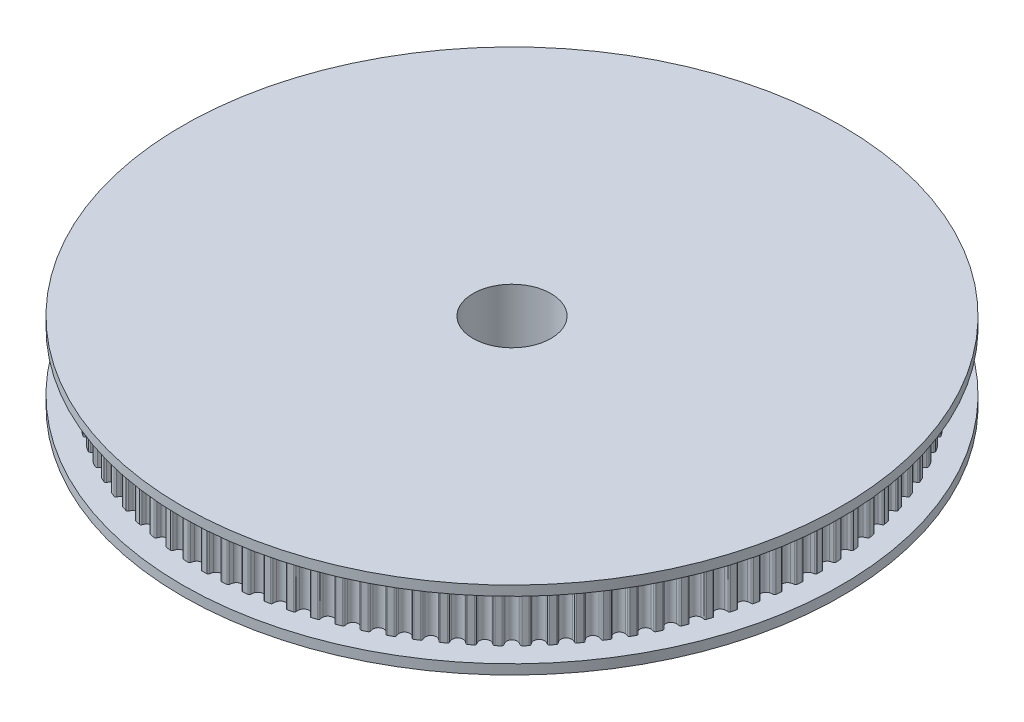
SolidWorks part; units mm, degrees
ref_plane "Front Plane" through (0, 0, 0) normal (0, 0, 1) x (1, 0, 0)
ref_plane "Top Plane" through (0, 0, 0) normal (0, 1, 0) x (1, 0, 0)
ref_plane "Right Plane" through (0, 0, 0) normal (1, 0, 0) x (0, 0, -1)
sketch "Sketch1" plane through (0, 0, 0) normal (0, 1, 0) x (1, 0, 0)
  circle A0 centre (0, 0) radius 31.831
  dimension "D1" = 63.662
extrude "Boss-Extrude1" add sketch "Sketch1" along normal mid plane 6
sketch "Sketch2" plane through (0, 0, 0) normal (0, 1, 0) x (1, 0, 0)
  line L0 (0, 0) -> (0, 31.577) construction
  line L1 (0, 0) -> (0.9857, 31.3665) construction
  line L2 (0, 31.577) -> (0, 31.831)
  line L3 (0.9857, 31.3665) -> (0.9998, 31.8153) construction
  line L4 (0.9998, 31.8153) -> (1.3996, 31.8002) construction
  line L5 (1.3996, 31.8002) -> (1.3902, 31.5521) construction
  line L6 (1.9827, 31.5147) -> (1.9987, 31.7682)
  arc A1 (0, 31.577) -> (0.2483, 31.576) centre (0, 0) cw
  arc A2 (0.2483, 31.576) -> (0.3962, 31.4425) centre (0.2471, 31.426) cw
  arc A3 (0.3962, 31.4425) -> (0.4813, 31.1351) centre (1.3902, 31.5521) ccw
  arc A4 (0.4813, 31.1351) -> (1.4746, 31.1038) centre (0.9857, 31.3665) ccw
  circle A5 centre (0, 0) radius 31.831 construction
  arc A6 (0, 31.831) -> (1.9987, 31.7682) centre (0, 0) cw
  arc A7 (1.5789, 31.4053) -> (1.4746, 31.1038) centre (0.5937, 31.5771) cw
  arc A8 (1.7349, 31.5293) -> (1.5789, 31.4053) centre (1.7266, 31.3795) ccw
  arc A9 (1.9827, 31.5147) -> (1.7349, 31.5293) centre (0, 0) ccw
  dimension "D2" = 0.15
  dimension "D3" = 1
  dimension "D4" = 0.555
  dimension "D1" = 1.8
  dimension "D5" = 0.254
  dimension "D6" = 0.4
  dimension "D7" = 1.004
extrude "Cut-Extrude1" cut sketch "Sketch2" against normal through all both and the other way through all
pattern_circular "CirPattern1" count 100 over 360 about axis through (0, 3, 0) along (0, -1, 0) of "Cut-Extrude1"
sketch "Sketch3" plane through (0, 0, 0) normal (0, 1, 0) x (1, 0, 0)
  circle A0 centre (0, 0) radius 33.831
  dimension "D1" = 67.662
extrude "Boss-Extrude2" add sketch "Sketch3" along normal blind 1 from surface starting at face at (0, 3, 0)
extrude "Boss-Extrude3" add sketch "Sketch3<2>" against normal blind 1 from surface starting at face at (0, -3, 0)
sketch "Sketch3<2>" plane through (0, 0, 0) normal (0, 1, 0) x (1, 0, 0) same geometry as "Sketch3"
sketch "Sketch4" plane through (0, 0, 0) normal (0, 1, 0) x (1, 0, 0)
  circle A0 centre (0, 0) radius 4
  dimension "D1" = 8
extrude "Cut-Extrude2" cut sketch "Sketch4" against normal through all both and the other way through all
equation "\"n\"= 100"
equation "\"p\"= 2mm"
equation "\"pd\"= ( \"n\" * \"p\" ) / pi"
equation "\"D1@Sketch1\"=\"pd\""
equation "\"D1@Sketch2\"=180/\"n\""
equation "\"D1@CirPattern1\"=\"n\""
equation "\"D1@Sketch3\"=\"pd\"+4mm"
